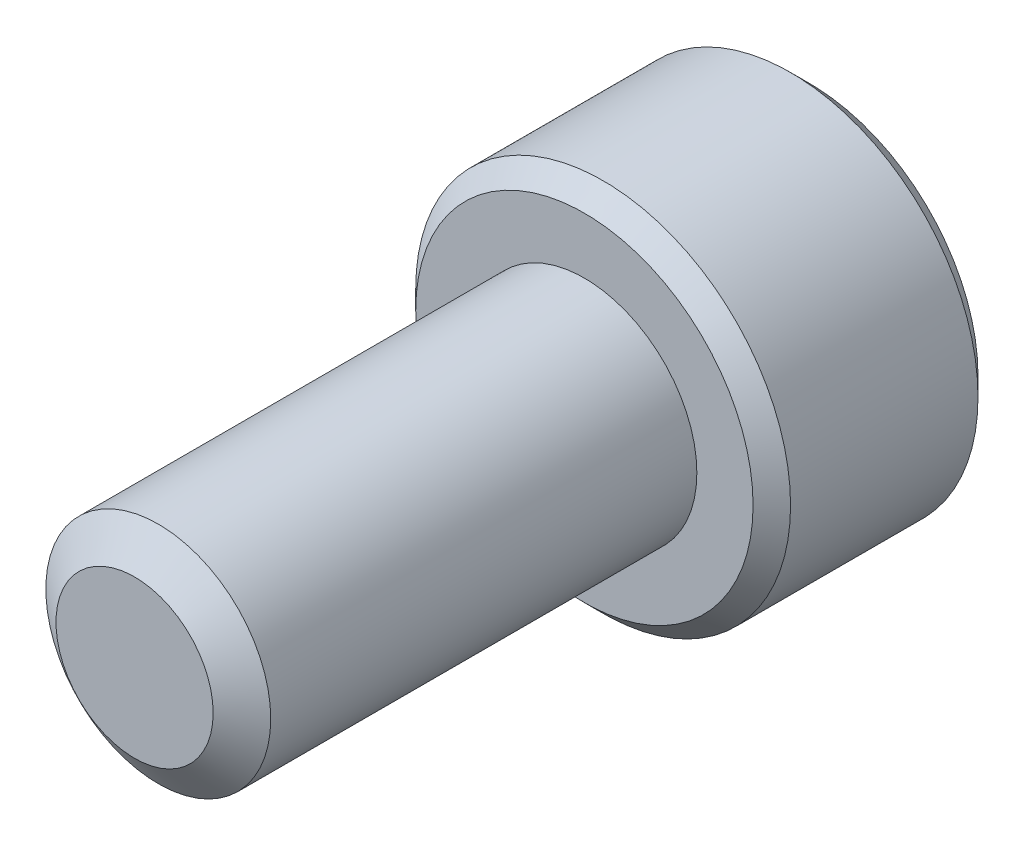
SolidWorks part; units mm, degrees
other "DetailItem1"
material "1.4310 (X10CrNi18-8)"
ref_plane "Front Plane" through (0, 0, 0) normal (0, 0, 1) x (1, 0, 0)
ref_plane "Top Plane" through (0, 0, 0) normal (0, 1, 0) x (1, 0, 0)
ref_plane "Right Plane" through (0, 0, 0) normal (1, 0, 0) x (0, 0, -1)
sketch "Sketch1" plane through (0, 0, 0) normal (0, 0, 1) x (1, 0, 0)
  circle A0 centre (0, 0) radius 3
  dimension "OD" = 6
extrude "Extrude1" add sketch "Sketch1" against normal blind 12
sketch "Sketch2" plane through (0, 0, 0) normal (0, 0, 1) x (1, 0, 0)
  circle A0 centre (0, 0) radius 3 construction
  circle A1 centre (0, 0) radius 3
curve "Helix/Spiral1" pitch 1 height 13 turns 13 parameters "pitch"=1
sketch "Sketch3" plane through (0, 0, 0) normal (1, 0, 0) x (0, 0, -1)
  line L0 (-0.875, 3) -> (-0.5, 2.3505)
  line L1 (-0.5, 2.3505) -> (-0.375, 2.3505)
  line L2 (-0.375, 2.3505) -> (0, 3)
  line L3 (-0.875, 3) -> (0, 3)
  line L4 (-0.4375, 3) -> (-0.4375, 2.3505) construction
  line L5 (-0.6875, 2.6752) -> (-0.1875, 2.6752) construction
  line L6 (0, 3) -> (0, -3) construction
  dimension "D1" = 0.125
  dimension "D2" = 0.5
  dimension "D3" = 60
sweep "Cut-Sweep1" [suppressed] cut profiles "Sketch3" path "Helix/Spiral1"
sketch "Sketch4" plane through (0, 0, 0) normal (1, 0, 0) x (0, 0, -1)
  line L0 (0.6327, 3) -> (0, 2.0965)
  line L1 (0, 2.0965) -> (0, 3)
  line L2 (0.6327, 3) -> (0, 3)
  line L3 (-0.875, 3) -> (0, 3) construction
  line L4 (0, 0) -> (7.0209, 0) construction
  dimension "D1" = 55
  dimension "D2" = 0.254
revolve "Cut-Revolve1" cut sketch "Sketch4" angle 360 about L4
sketch "Sketch6" plane through (0, 0, -12) normal (0, 0, -1) x (-1, 0, 0)
  circle A0 centre (0, 0) radius 5
  dimension "head dia" = 10
extrude "Extrude2" add sketch "Sketch6" along normal blind 6
sketch "Sketch7" plane through (0, 0, -18) normal (0, 0, -1) x (-1, 0, 0)
  line L1 (0, 2.8868) -> (-2.5, 1.4434)
  line L2 (-2.5, 1.4434) -> (-2.5, -1.4434)
  line L3 (-2.5, -1.4434) -> (0, -2.8868)
  line L4 (0, -2.8868) -> (2.5, -1.4434)
  line L5 (2.5, -1.4434) -> (2.5, 1.4434)
  line L6 (2.5, 1.4434) -> (0, 2.8868)
  circle A0 centre (0, 0) radius 2.5 construction
  dimension "hex dia" = 5
extrude "Cut-Extrude1" cut sketch "Sketch7" against normal blind 3.75
sketch "Sketch8" plane through (0, 0, -18) normal (0, 0, -1) x (-1, 0, 0)
  circle A0 centre (0, 0) radius 2.8868
extrude "Cut-Extrude2" cut sketch "Sketch8" against normal through all draft 45
chamfer "Chamfer1" distance 0.5 angle 45 2 edges at (-5, 0, -18) (-5, 0, -12)
sketch "Sketch10" plane through (0, 0, -12) normal (0, 0, 1) x (1, 0, 0)
  circle A1 centre (0, 0) radius 3
  circle A2 centre (0, 0) radius 3
  dimension "D1" = 0
ref_plane "Plane1" through (0, 0, 0) normal (0, 0, 1) x (1, 0, 0)
extrude "partial thread" [suppressed] add sketch "Sketch10" along normal up to surface (31 mm away) separate body up to plane "Plane1"
chamfer "Chamfer2" [suppressed] distance 0.12 angle 45
combine bodies "Combine1" [suppressed] operation type add bodies to combine 107 108
sketch "Sketch9" plane through (0, 0, 0) normal (1, 0, 0) x (0, 0, -1)
  line L0 (0, 3) -> (0, -3) construction
  line L1 (2.5, 3) -> (2.5, -3) construction
  dimension "D1" = 2.5
equation "\"D3@Helix/Spiral1\" = \"screw length@Extrude1\"+\"pitch@Helix/Spiral1\""
equation "\"D1@Sketch3\" = \"pitch@Helix/Spiral1\"*.125"
equation "\"D2@Sketch3\" = \"pitch@Helix/Spiral1\"*.5"
equation "\"D1@Cut-Extrude1\" = \"hex dia@Sketch7\"*.75"
equation "\"D1@Chamfer1\" = \"head dia@Sketch6\"*.05"
equation "\"D1@Sketch9\" = \"pitch@Helix/Spiral1\"*2.5"
equation "\"D1@Chamfer2\"=\"OD@Sketch1\"*.02"
